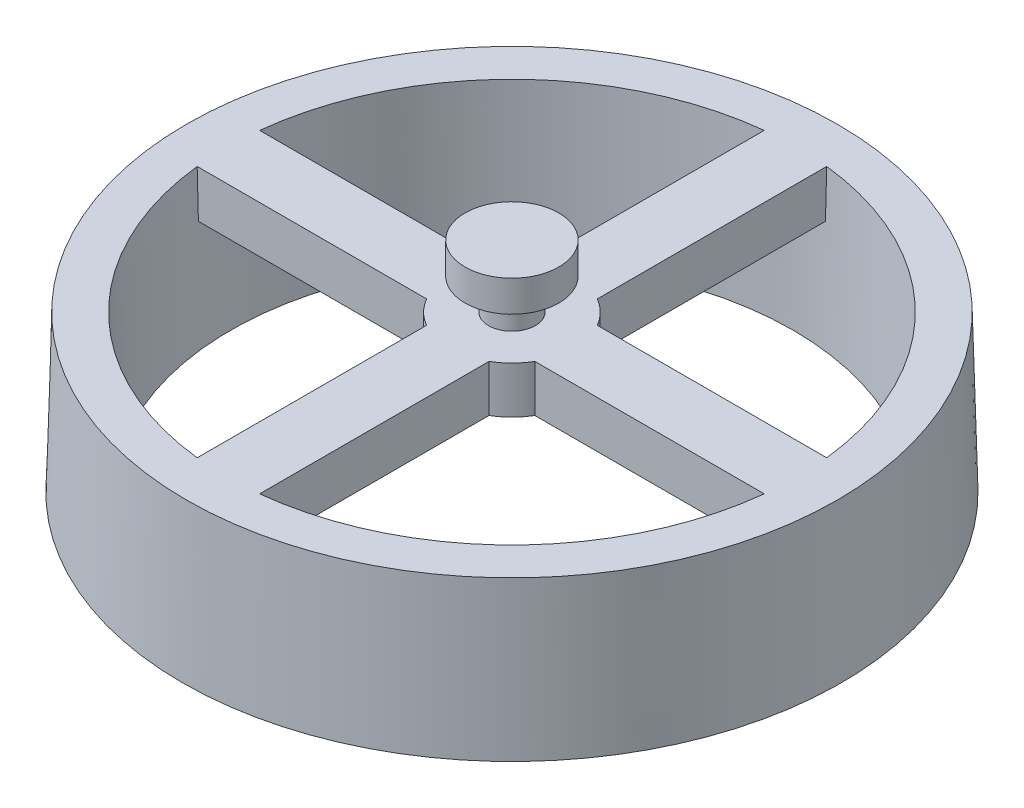
SolidWorks part; units mm, degrees
ref_plane "Front Plane" through (0, 0, 0) normal (0, 0, 1) x (1, 0, 0)
ref_plane "Top Plane" through (0, 0, 0) normal (0, 1, 0) x (1, 0, 0)
ref_plane "Right Plane" through (0, 0, 0) normal (1, 0, 0) x (0, 0, -1)
ref_axis "Axis1" through (0, 5.25, 0) along (0, -1, 0)
sketch "Sketch1" plane through (0, 0, 0) normal (0, 1, 0) x (1, 0, 0)
  circle A0 centre (0, 0) radius 10.55
  circle A1 centre (0, 0) radius 9
extrude "Extrude1" add sketch "Sketch1" along normal blind 5 draft 1.5
sketch "Sketch4" plane through (0, 5, 0) normal (0, 1, 0) x (1, 0, 0)
  line L1 (-1, 9.5) -> (1, 9.5)
  line L2 (-1, 9.5) -> (-1, 1.7321)
  line L4 (1, 9.5) -> (1, 1.7321)
  arc A0 (-1, 1.7321) -> (1, 1.7321) centre (0, 0) ccw
extrude "Extrude3" add sketch "Sketch4" against normal blind 1.5
pattern_circular "CirPattern1" count 4 over 360 about axis through (0, 5.25, 0) along (0, -1, 0) of "Extrude3"
sketch "Sketch5" plane through (0, 5, 0) normal (0, 1, 0) x (1, 0, 0)
  circle A0 centre (0, 0) radius 0.75
extrude "Extrude4" add sketch "Sketch5" along normal blind 1
sketch "Sketch6" plane through (0, 6, 0) normal (0, 1, 0) x (1, 0, 0)
  circle A0 centre (0, 0) radius 1.5
extrude "Extrude5" add sketch "Sketch6" along normal blind 1
